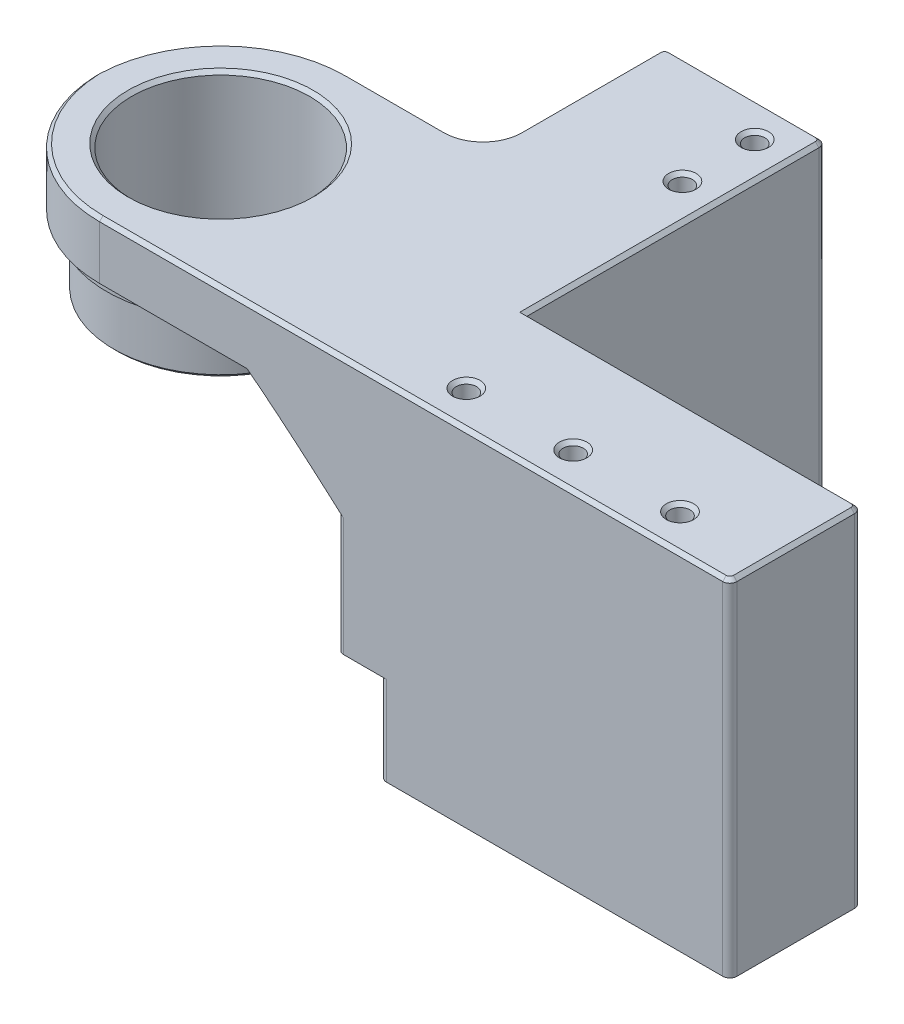
SolidWorks part; units mm, degrees
ref_plane "Front Plane" through (0, 0, 0) normal (0, 0, 1) x (1, 0, 0)
ref_plane "Top Plane" through (0, 0, 0) normal (0, 1, 0) x (1, 0, 0)
ref_plane "Right Plane" through (0, 0, 0) normal (1, 0, 0) x (0, 0, -1)
sketch "Sketch1" plane through (0, 0, 0) normal (0, 1, 0) x (1, 0, 0)
  line L0 (60.6181, 17.7752) -> (49.3328, 24.1377) construction
  line L2 (-17.5, 17.5) -> (-17.5, -17.5)
  line L5 (47.5, 37.5) -> (78.5, 37.5) construction
  line L6 (47.5, 37.5) -> (47.5, 6.5) construction
  line L7 (47.5, 6.5) -> (78.5, 6.5) construction
  line L8 (78.5, 37.5) -> (78.5, 6.5) construction
  line L9 (64.0945, 26.7249) -> (9.1398, 39.4552) construction
  line L10 (42.2652, 20.3799) -> (40.3703, -3.2389) construction
  line L11 (63, 22) -> (63, 43) construction
  line L12 (84, 43) -> (42, 43) construction
  line L13 (84, 43) -> (84, 1) construction
  line L14 (84, 1) -> (42, 1) construction
  line L15 (42, 43) -> (42, 1) construction
  line L16 (63, 22) -> (84, 22) construction
  line L17 (-12.5, -1000) -> (-12.5, 49000) construction
  line L18 (-1001.6818, 12.5) -> (48998.3182, 12.5) construction
  line L19 (-991.5, -12.5) -> (49008.5, -12.5) construction
  line L20 (-17.5, -17.5) -> (89, -17.5)
  line L21 (89, 1) -> (89, -17.5)
  line L23 (78.5, 37.5) -> (82.5, 37.5) construction
  line L26 (78.5, 39) -> (82.5, 39) construction
  line L29 (78.5, 36) -> (82.5, 36) construction
  line L40 (-17.5, 17.5) -> (19.3317, 17.5)
  line L41 (19.3317, 17.5) -> (19.3317, 43)
  line L43 (84, -966.1083) -> (84, 49033.8917) construction
  line L44 (19.3317, 43) -> (-79.4, 43) construction
  line L45 (19.3317, 38) -> (89, 38) construction
  line L46 (19.3317, 43) -> (42, 43)
  line L47 (42, 43) -> (42, 1)
  line L48 (42, 1) -> (89, 1)
  circle A0 centre (0, 0) radius 21 construction
  circle A1 centre (47.5, 37.5) radius 1.5 construction
  circle A2 centre (78.5, 37.5) radius 1.5 construction
  circle A3 centre (78.5, 6.5) radius 1.5 construction
  circle A4 centre (47.5, 6.5) radius 1.5 construction
  circle A5 centre (63, 22) radius 8 construction
  circle A9 centre (47, 20) radius 1.5 construction
  circle A10 centre (47, 20) radius 6.5 construction
  circle A11 centre (0, 0) radius 42 construction
  arc A12 (40.3703, -3.2389) -> (9.1398, 39.4552) centre (0, 0) cw construction
  arc A13 (42.2652, 20.3799) -> (49.3328, 24.1377) centre (47, 20) cw construction
  arc A14 (64.0945, 26.7249) -> (60.6181, 17.7752) centre (63, 22) cw construction
  circle A15 centre (63, 22) radius 7 construction
  circle A26 centre (0, 0) radius 12.5
  circle A27 centre (47, -12.5) radius 1.425
  circle A28 centre (62, -12.5) radius 1.425
  circle A29 centre (77, -12.5) radius 1.425
  circle A30 centre (37, 38) radius 1.425
  circle A31 centre (37, 27.8373) radius 1.425
  arc A32 (78.5, 39) -> (78.5, 36) centre (78.5, 37.5) ccw construction
  arc A33 (82.5, 36) -> (82.5, 39) centre (82.5, 37.5) ccw construction
  point P17 (47.5, 22)
  point P18 (63, 37.5)
  point P19 (80.5, 37.5)
  point P27 (63, 43)
  point P47 (0, 0)
  dimension "D1" = 42
  dimension "D2" = 16
  dimension "D4" = 3
  dimension "D5" = 40.5
  dimension "D6" = 4.85
  dimension "D7" = 4.75
  dimension "D9" = 3
  dimension "D14" = 13
  dimension "D15" = 84
  dimension "D13" = 14
  dimension "D18" = 25
  dimension "D23" = 2.85
  dimension "D3" = 31
  dimension "D8" = 42
  dimension "D10" = 5
  dimension "D11" = 5
  dimension "D12" = 5
  dimension "D16" = 4
  dimension "D17" = 5
  dimension "D19" = 63
  dimension "D20" = 44
  dimension "D21" = 20
  dimension "D22" = 47
  dimension "D24" = 5
  dimension "D26" = 10.1627
  dimension "D27" = 5
  dimension "D25" = 3
extrude "Boss-Extrude1" add sketch "Sketch1" along normal blind 8
sketch "Sketch2" plane through (0, 0, 0) normal (0, -1, 0) x (1, 0, 0)
  circle A2 centre (0, 0) radius 16
  circle A3 centre (0, 0) radius 12.5 construction
  circle A4 centre (0, 0) radius 12.5
  dimension "D1" = 32
extrude "Boss-Extrude2" add sketch "Sketch2" along normal blind 2
sketch "Sketch6" plane through (0, -2, 0) normal (0, -1, 0) x (-1, 0, 0)
  circle A0 centre (0, 0) radius 12.5 construction
  circle A1 centre (0, 0) radius 12.5
  circle A2 centre (0, 0) radius 15
  dimension "D1" = 30
fillet "Fillet5" radius 18 2 edges at (-17.5, 4, -17.5) (-17.5, 4, 17.5)
extrude "Boss-Extrude4" add sketch "Sketch6" along normal blind 8
sketch "Sketch11" plane through (0, 0, 0) normal (0, -1, 0) x (1, 0, 0)
  line L0 (47, 12.5) -> (77, 12.5) construction
  line L1 (47, 17.5) -> (77, 17.5) construction
  line L2 (47, 7.5) -> (77, 7.5) construction
  line L3 (-17.5, 17.5) -> (89, 17.5) construction
  line L5 (42, -1) -> (89, -1) construction
  line L7 (89, -1) -> (89, 17.5)
  line L8 (89, 17.5) -> (39.2779, 17.5)
  line L10 (42, -30.3034) -> (26.4449, -33.9067)
  line L11 (42, -43) -> (42, -1) construction
  line L12 (64.0945, -26.7249) -> (9.1398, -39.4552) construction
  line L13 (42, -30.3034) -> (42, -26.245)
  line L14 (36.4343, -22.8373) -> (39.52, -22.8373)
  line L15 (42, -33.3828) -> (19.3317, -38.634)
  line L16 (19.3317, -17.5) -> (19.3317, -43) construction
  line L17 (19.3317, -38.634) -> (19.3317, -43)
  line L18 (19.3317, -43) -> (42, -43)
  line L19 (42, -43) -> (42, -33.3828)
  line L20 (89, -1) -> (42.9884, -1)
  arc A0 (47, 17.5) -> (47, 7.5) centre (47, 12.5) ccw construction
  arc A1 (77, 7.5) -> (77, 17.5) centre (77, 12.5) ccw construction
  circle A3 centre (0, 0) radius 42 construction
  circle A4 centre (0, 0) radius 42 construction
  circle A5 centre (0, 0) radius 43 construction
  circle A6 centre (47, -20) radius 6.5 construction
  circle A7 centre (47, -20) radius 6.5 construction
  circle A8 centre (47, -20) radius 8 construction
  circle A9 centre (37, -27.8373) radius 1.425 construction
  circle A10 centre (37, -27.8373) radius 1.425
  circle A11 centre (37, -38) radius 1.425 construction
  circle A12 centre (37, -38) radius 1.425
  arc A13 (42, -26.245) -> (39.52, -22.8373) centre (47, -20) cw
  arc A14 (36.4343, -22.8373) -> (26.4449, -33.9067) centre (0, 0) cw
  circle A15 centre (77, 12.5) radius 1.425 construction
  circle A16 centre (62, 12.5) radius 1.425 construction
  circle A17 centre (47, 12.5) radius 1.425 construction
  circle A18 centre (77, 12.5) radius 1.425
  circle A19 centre (62, 12.5) radius 1.425
  circle A20 centre (47, 12.5) radius 1.425
  arc A21 (39.2779, 17.5) -> (42.9884, -1) centre (0, 0) cw
  point P4 (62, 12.5)
  dimension "D3" = 1.5
  dimension "D4" = 5
  dimension "D5" = 1.5
  dimension "D1" = 1
  dimension "D2" = 1.5
extrude "Boss-Extrude7" add sketch "Sketch11" along normal blind 40.5
sketch "Sketch14" plane through (0, 0, 0) normal (0, -1, 0) x (1, 0, 0)
  line L5 (19.3317, -17.5) -> (19.3317, -43) construction
  line L6 (-17.5, 17.5) -> (89, 17.5) construction
  line L7 (39.2779, 17.5) -> (33.1662, 17.5)
  line L8 (42.9884, -1) -> (42, -1)
  line L9 (42, -1) -> (42, -43)
  line L10 (42, -43) -> (19.3317, -43)
  line L11 (19.3317, -43) -> (19.3317, -32.1331)
  circle A0 centre (0, 0) radius 37.5 construction
  arc A1 (19.3317, -32.1331) -> (33.1662, 17.5) centre (0, 0) ccw
  arc A2 (42.9884, -1) -> (39.2779, 17.5) centre (0, 0) ccw construction
  arc A3 (42.9884, -1) -> (39.2779, 17.5) centre (0, 0) ccw
  circle A4 centre (37, -38) radius 1.425 construction
  circle A5 centre (37, -27.8373) radius 1.425 construction
  circle A6 centre (37, -38) radius 1.425
  circle A7 centre (37, -27.8373) radius 1.425
  dimension "D1" = 75
extrude "Boss-Extrude8" add sketch "Sketch14" along normal offset from surface (28 mm away) 12.5 up to face at (37.3309, -40.5, -27.3464)
chamfer "Chamfer6" distance 10 angle 45 1 edges at (36.123, 0, -10.0688)
fillet "Fillet10" radius 1 12 edges at (89, -16.25, 17.5) (89, -16.25, -1) (42.9884, -34.25, -1) (39.2779, -34.25, 17.5) (42, -16.25, -43) (42, -34.25, -30.3034) (42, -34.25, -33.3828) (19.3317, -16.25, -43) (19.3317, -34.25, -38.634) (26.4449, -34.25, -33.9067) (33.1662, -19, 17.5) (19.3317, -19, -32.1331) tangent propagation no
chamfer "Chamfer5" distance 0.5 angle 45 1 edges at (0, -10, -15)
fillet "Fillet6" radius 5 1 edges at (19.3317, 4, -17.5)
chamfer "Chamfer2" distance 0.5 angle 45 20 edges at (37, 8, -26.4123) (77, 8, 13.925) (0, 8, 12.5) (30.6658, 8, -43) (42, 8, -21.5) (65, 8, -1) (44.25, 8, 17.5) (-12.0499, 8, 12.4035) (-12.0499, 8, -12.4035) (7.4158, 8, -17.5) (17.8672, 8, -18.9645) (19.3317, 8, -32.25) (47, 8, 13.925) (62, 8, 13.925) (37, 8, -36.575) (89, 8, 8.25) (19.6246, 8, -42.7071) (41.7071, 8, -42.7071) (88.7071, 8, -0.7071) (88.7071, 8, 17.2071)
